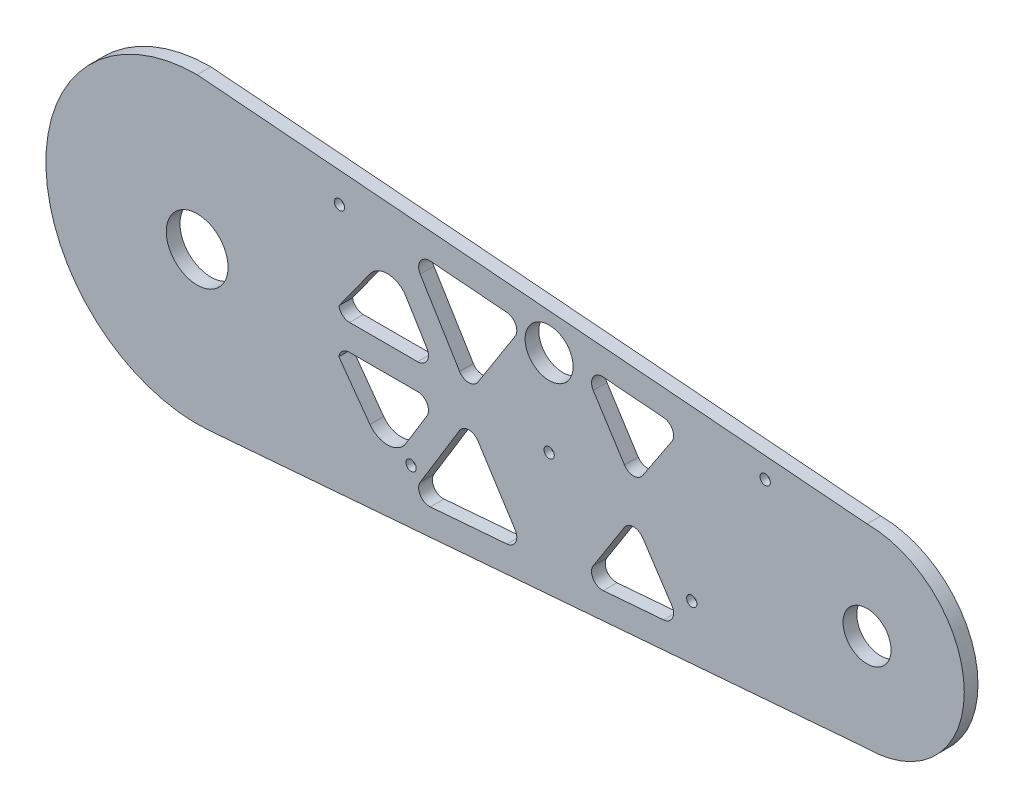
SolidWorks part; units mm, degrees
other "Marca1"
sketch "Croquis3" plane through (-70, -70, 6.35) normal (0, 0, 1) x (1, 0, 0)
material "6061-O (SS)"
ref_plane "Front Plane" through (0, 0, 0) normal (0, 0, 1) x (1, 0, 0)
ref_plane "Top Plane" through (0, 0, 0) normal (0, 1, 0) x (1, 0, 0)
ref_plane "Right Plane" through (0, 0, 0) normal (1, 0, 0) x (0, 0, -1)
sketch "Sketch1" plane through (0, 0, 0) normal (0, 0, 1) x (1, 0, 0)
  line L0 (0, 70) -> (310, 45)
  line L1 (5.1714, -69.8087) -> (310, -45)
  line L2 (0, 0) -> (310, 0) construction
  line L3 (107.899, 49.2595) -> (143.3142, 46.4034)
  line L4 (70.5232, 6) -> (102.03, 6)
  line L5 (219.6238, 32.8105) -> (206.1309, 12.4175)
  line L6 (197.7459, 12.4871) -> (183.2969, 35.1335)
  line L7 (162.8785, 6) -> (162.8785, -6) construction
  line L8 (258.6323, 64.5867) -> (258.6323, 39.5867) construction
  line L9 (147.1275, 38.7303) -> (129.9162, 11.7546)
  line L10 (121.433, 11.8395) -> (103.229, 41.6712)
  line L11 (98.117, 50.0484) -> (42.0027, 50.0484) construction
  line L12 (187.9139, 42.8067) -> (215.8558, 40.5533)
  line L13 (162.8785, 44.8257) -> (162.8785, 6) construction
  line L14 (67.1248, 64.5867) -> (162.8785, 40) construction
  line L15 (201.8849, 6) -> (201.8849, 41.68) construction
  line L16 (125.6066, 5) -> (125.6066, 47.8315) construction
  line L17 (96.5904, 29.5131) -> (106.2981, 13.6045)
  line L18 (125.6066, -5) -> (125.6066, -47.8315) construction
  line L19 (201.8849, -6) -> (201.8849, -41.68) construction
  line L20 (162.8785, -44.8257) -> (162.8785, -6) construction
  line L21 (98.117, -50.0484) -> (42.0027, -50.0484) construction
  line L22 (96.5904, -29.5131) -> (106.2981, -13.6045)
  line L23 (67.1248, 64.5867) -> (409.6974, 64.5867) construction
  line L24 (187.9139, -42.8067) -> (215.8558, -40.5533)
  line L25 (121.433, -11.8395) -> (103.229, -41.6712)
  line L26 (147.1275, -38.7303) -> (129.9162, -11.7546)
  line L27 (162.8785, 0) -> (258.6323, 64.5867) construction
  line L28 (67.1248, 64.5867) -> (67.1248, 39.5867) construction
  line L29 (197.7459, -12.4871) -> (183.2969, -35.1335)
  line L30 (219.6238, -32.8105) -> (206.1309, -12.4175)
  line L31 (70.5232, -6) -> (102.03, -6)
  line L32 (107.899, -49.2595) -> (143.3142, -46.4034)
  line L33 (0, -6.35) -> (0, 6.35) construction
  line L34 (67.1248, 39.5867) -> (162.8785, 40) construction
  line L35 (162.8785, 40) -> (68.3705, 24.1395) construction
  line L36 (79.9417, 30.1512) -> (65.583, 10.2294)
  line L37 (79.9417, -30.1512) -> (65.583, -10.2294)
  arc A0 (65.583, 10.2294) -> (70.5232, 6) centre (70.5232, 11) ccw
  arc A1 (310, -45) -> (310, 45) centre (310, 0) ccw
  circle A2 centre (0, 0) radius 14.2938
  circle A3 centre (310, 0) radius 11.11
  arc A4 (79.9417, 30.1512) -> (96.5904, 29.5131) centre (88.0542, 24.3041) cw
  arc A5 (79.9417, -30.1512) -> (96.5904, -29.5131) centre (88.0542, -24.3041) ccw
  arc A6 (0, 70) -> (5.1714, -69.8087) centre (0, 0) ccw
  arc A7 (187.9139, 42.8067) -> (183.2969, 35.1335) centre (187.512, 37.8229) ccw
  arc A8 (219.6238, 32.8105) -> (215.8558, 40.5533) centre (215.4539, 35.5695) ccw
  arc A9 (206.1309, 12.4175) -> (197.7459, 12.4871) centre (201.961, 15.1765) cw
  circle A10 centre (162.8785, 40) radius 11.1125
  arc A13 (102.03, 6) -> (106.2981, 13.6045) centre (102.03, 11) ccw
  arc A14 (121.433, 11.8395) -> (129.9162, 11.7546) centre (125.7011, 14.444) ccw
  arc A15 (147.1275, 38.7303) -> (143.3142, 46.4034) centre (142.9123, 41.4196) ccw
  arc A16 (107.899, 49.2595) -> (103.229, 41.6712) centre (107.4971, 44.2757) ccw
  arc A17 (107.899, -49.2595) -> (103.229, -41.6712) centre (107.4971, -44.2757) cw
  arc A18 (147.1275, -38.7303) -> (143.3142, -46.4034) centre (142.9123, -41.4196) cw
  arc A19 (121.433, -11.8395) -> (129.9162, -11.7546) centre (125.7011, -14.444) cw
  arc A20 (102.03, -6) -> (106.2981, -13.6045) centre (102.03, -11) cw
  arc A24 (206.1309, -12.4175) -> (197.7459, -12.4871) centre (201.961, -15.1765) ccw
  arc A25 (219.6238, -32.8105) -> (215.8558, -40.5533) centre (215.4539, -35.5695) cw
  arc A26 (187.9139, -42.8067) -> (183.2969, -35.1335) centre (187.512, -37.8229) cw
  arc A29 (65.583, -10.2294) -> (70.5232, -6) centre (70.5232, -11) cw
  point P31 (177.8851, 43.6155)
  point P42 (187.6504, 6)
  point P44 (88.7465, 42.3671)
  point P45 (138.1067, 6)
  point P79 (88.7465, -42.3671)
  point P100 (138.1067, -6)
  point P101 (187.6504, -6)
  point P102 (177.8851, -43.6155)
  point P104 (0, 0)
  point P114 (310, 0)
  point P119 (0.2114, 0.3175)
  dimension "D2" = 45
  dimension "D3" = 12.7
  dimension "D4" = 22.22
  dimension "D6" = 12
  dimension "D11" = 5
  dimension "D12" = 70
  dimension "D13" = 25
  dimension "D8" = 5
  dimension "D14" = 12
  dimension "D15" = 25
  dimension "D16" = 310
  dimension "D17" = 22.225
  dimension "D5" = 28.5877
  dimension "D19" = 10
  dimension "D20" = 10
  dimension "D7" = 6
  dimension "D9" = 9.279
  dimension "D10" = 34
  dimension "D18" = 40
extrude "Boss-Extrude1" add sketch "Sketch1" along normal blind 6.35
sketch "Sketch2" plane through (0, 0, 6.35) normal (0, 0, 1) x (1, 0, 0)
  line L0 (263.0927, 39.4927) -> (-0.4655, 64.9983)
  line L1 (4.6885, -64.8307) -> (263.1366, -39.5384)
  arc A0 (-0.4655, 64.9983) -> (4.6885, -64.8307) centre (0, 0) ccw
  arc A1 (263.1366, -39.5384) -> (270.3186, -23.7999) centre (262.1626, -29.5859) ccw
  circle A2 centre (0, 0) radius 40
  arc A3 (270.292, 23.7623) -> (270.3186, -23.7999) centre (303.867, 0) ccw
  arc A4 (270.292, 23.7623) -> (263.0927, 39.4927) centre (262.1295, 29.5392) ccw
  dimension "D1" = 10
  dimension "D2" = 41.133
  dimension "D3" = 65
ref_plane "Plane1" through (0, 0, 10) normal (0, 0, 1) x (1, 0, 0)
sketch "Croquis1" plane through (0, 0, 6.35) normal (0, 0, 1) x (1, 0, 0)
  circle A1 centre (98.9956, -37.0901) radius 2.3813
  circle A2 centre (228.8774, -26.5196) radius 2.3813
  point P20 (0, 0)
  dimension "D5" = 4.7625
  dimension "D1" = 4.7625
extrude "Cortar-Extruir1" cut sketch "Croquis1" against normal blind 50
sketch "Croquis4" plane through (0, 0, 0) normal (0, 0, -1) x (-1, 0, 0)
  circle A0 centre (-228.8774, -26.5196) radius 5
  circle A1 centre (-98.9956, -37.0901) radius 5
  dimension "D1" = 10
extrude "Cortar-Extruir2" cut sketch "Croquis4" against normal blind 3.175
sketch "Croquis5" plane through (0, 0, 0) normal (0, 0, -1) x (-1, 0, 0)
  line L0 (-162.8785, 40) -> (-162.8785, -35.6506) construction
  line L1 (-193.2674, -35.6506) -> (-132.4897, -35.6506) construction
  circle A0 centre (-162.8785, 0) radius 5
  point P6 (-162.8785, -35.6506)
  dimension "D2" = 10
  dimension "D1" = 40
extrude "Cortar-Extruir3" cut sketch "Croquis5" against normal blind 3.175
sketch "Croquis6" plane through (0, 0, 0) normal (0, 0, -1) x (-1, 0, 0)
  circle A0 centre (-162.8785, 0) radius 2.3813
  dimension "D1" = 4.7625
extrude "Cortar-Extruir4" cut sketch "Croquis6" against normal blind 10
sketch "Croquis7" plane through (0, 0, 0) normal (0, 0, -1) x (-1, 0, 0)
  line L0 (-228.8774, -26.5196) -> (-98.9956, -37.0901) construction
  line L1 (-98.9956, -37.0901) -> (-65.8414, 50.869) construction
  line L2 (-228.8774, -26.5196) -> (-262.8716, 39.2101) construction
  circle A0 centre (-65.8414, 50.869) radius 2.3813
  circle A1 centre (-262.8716, 39.2101) radius 2.3813
  dimension "D5" = 4.7625
  dimension "D1" = 94
  dimension "D2" = 106
  dimension "D3" = 74
  dimension "D4" = 238
extrude "Cortar-Extruir5" cut sketch "Croquis7" against normal blind 10
sketch "Croquis8" plane through (0, 0, 0) normal (0, 0, -1) x (-1, 0, 0)
  circle A0 centre (-262.8716, 39.2101) radius 5
  circle A1 centre (-65.8414, 50.869) radius 5
  dimension "D1" = 10
  dimension "D2" = 10
extrude "Cortar-Extruir6" cut sketch "Croquis8" against normal blind 3.16
